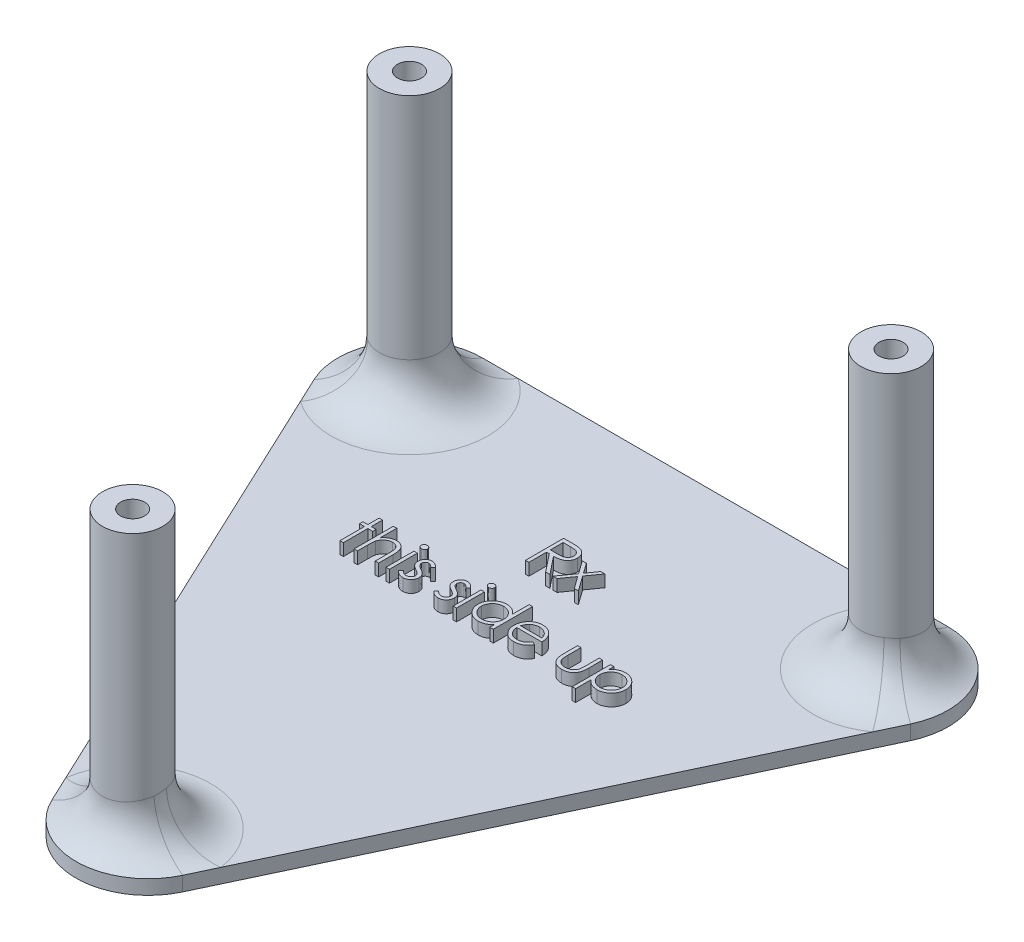
SolidWorks part; units mm, degrees
ref_plane "Front Plane" through (0, 0, 0) normal (0, 0, 1) x (1, 0, 0)
ref_plane "Top Plane" through (0, 0, 0) normal (0, 1, 0) x (1, 0, 0)
ref_plane "Right Plane" through (0, 0, 0) normal (1, 0, 0) x (0, 0, -1)
sketch "Sketch1" plane through (0, 0, 0) normal (0, 1, 0) x (1, 0, 0)
  line L0 (-68.8117, 40.7165) -> (-30.1211, 40.7165)
  line L1 (-24.6922, 32.1617) -> (-44.0375, -8.9471)
  line L2 (-54.8953, -8.9471) -> (-74.2406, 32.1617)
  circle A0 centre (-49.4664, -7.6835) radius 1
  circle A1 centre (-29.4664, 35.3165) radius 1
  circle A2 centre (-69.4664, 35.3165) radius 1
  circle A3 centre (-49.4664, -7.6835) radius 2.5
  circle A4 centre (-29.4664, 35.3165) radius 2.5
  circle A5 centre (-69.4664, 35.3165) radius 2.5
  arc A6 (-44.0375, -8.9471) -> (-54.8953, -8.9471) centre (-49.4664, -6.3923) cw
  arc A7 (-74.2406, 32.1617) -> (-68.8117, 40.7165) centre (-68.8117, 34.7165) cw
  arc A8 (-24.6922, 32.1617) -> (-30.1211, 40.7165) centre (-30.1211, 34.7165) ccw
  point P12 (-49.4664, 40.7165)
  point P18 (-49.4664, -20.4835)
  point P21 (-78.2664, 40.7165)
  point P24 (-20.6664, 40.7165)
  dimension "D1" = 2
  dimension "D2" = 5
  dimension "D3" = 2
  dimension "D4" = 5
  dimension "D5" = 2
  dimension "D6" = 5
  dimension "D13" = 6
  dimension "D7" = 20
  dimension "D8" = 43
  dimension "D9" = 20
  dimension "D10" = 12.8
  dimension "D11" = 57.6
  dimension "D12" = 61.2
extrude "Boss-Extrude1" add sketch "Sketch1" against normal blind 1.2 contours L1 A8 L0 A7 L2 A6 A3 A4 A5 | A5 A2 | A2 | A4 A1 | A1 | A3 A0 | A0 region at (-49.4664, 0, -20.5977) region at (-49.4664, 0, 7.6835) region at (-29.4664, 0, -35.3165) region at (-69.4664, 0, -35.3165) region at (-51.8957, 0, 7.6835) region at (-31.8957, 0, -35.3165) region at (-71.8957, 0, -35.3165)
extrude "Boss-Extrude2" add sketch "Sketch1<3>" along normal blind 23 contours A5 A2 | A0 | A4 A1 | A3 region at (-49.4664, 0, 7.6835) region at (-31.8957, 0, -35.3165) region at (-71.8957, 0, -35.3165)
sketch "Sketch1<3>" plane through (0, 0, 0) normal (0, 1, 0) x (1, 0, 0) same geometry as "Sketch1"
fillet "Fillet1" radius 4 3 edges at (-49.4664, 0, 10.1835) (-69.4664, 0, -32.8165) (-29.4664, 0, -32.8165)
sketch "Sketch2" plane through (0, 0, 0) normal (0, 1, 0) x (1, 0, 0)
  line L0 (-71.784, 26.9413) -> (-27.1489, 26.9413) construction
  line L1 (-55.906, -6.7994) -> (-73.232, 30.0183) construction
  line L2 (-25.7008, 30.0183) -> (-43.0268, -6.7994) construction
  text T0 "Rx\r\nthis side up" font "Century Gothic" height 3.175
extrude "Boss-Extrude3" add sketch "Sketch2" along normal blind 1
